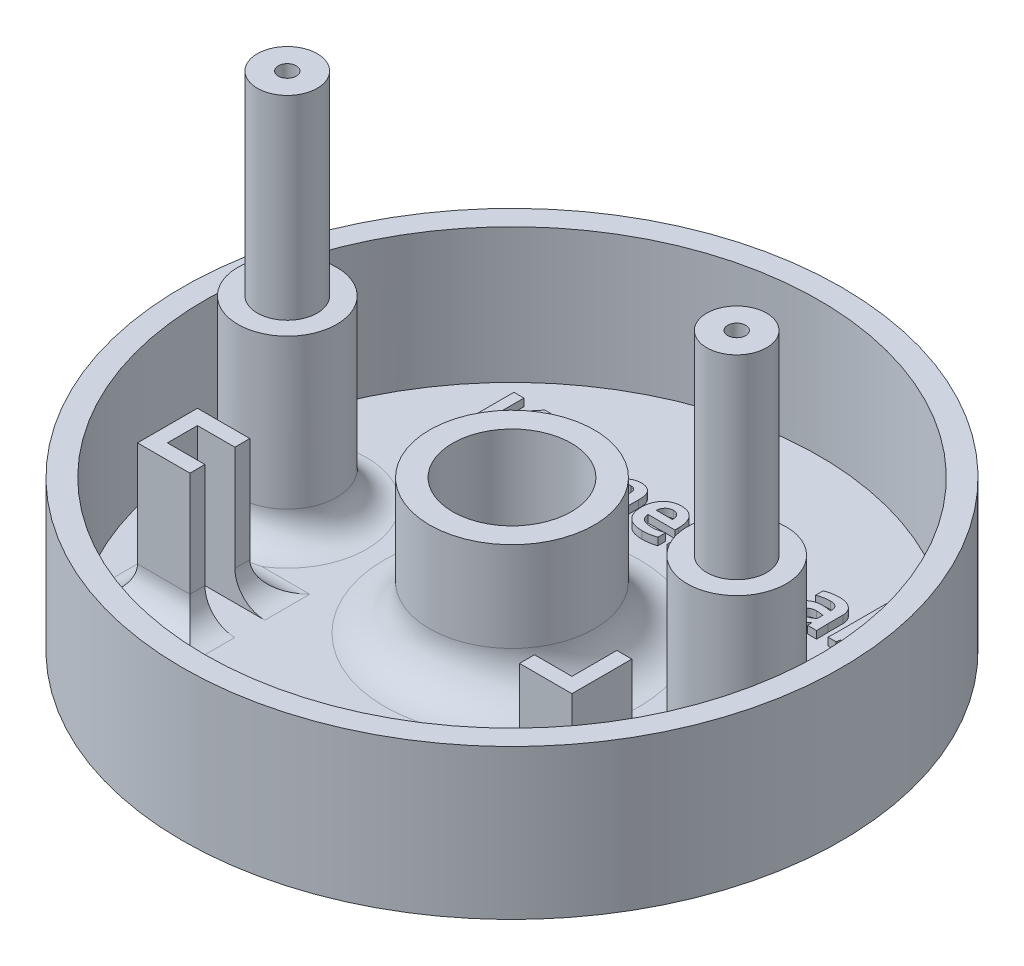
SolidWorks part; units mm, degrees
ref_plane "Front Plane" through (0, 0, 0) normal (0, 0, 1) x (1, 0, 0)
ref_plane "Top Plane" through (0, 0, 0) normal (0, 1, 0) x (1, 0, 0)
ref_plane "Right Plane" through (0, 0, 0) normal (1, 0, 0) x (0, 0, -1)
sketch "Sketch1" plane through (0, 0, 0) normal (0, 1, 0) x (1, 0, 0)
  line L0 (0, 0) -> (0, 22) construction
  line L1 (14.5, -6.5) -> (-14.5, -6.5)
  line L2 (-14.5, -6.5) -> (-14.5, -10.5)
  line L3 (-14.5, -10.5) -> (14.5, -10.5)
  line L4 (14.5, -10.5) -> (14.5, -6.5)
  line L5 (-11, -6.5) -> (-11, -7.5)
  line L6 (11, -6.5) -> (11, -7.5)
  line L9 (-11, -9.5) -> (-11, -10.5)
  line L10 (11, -9.5) -> (11, -10.5)
  line L13 (-13.5, -7.5) -> (13.5, -7.5)
  line L14 (-13.5, -7.5) -> (-13.5, -9.5)
  line L15 (-13.5, -9.5) -> (13.5, -9.5)
  line L16 (13.5, -7.5) -> (13.5, -9.5)
  line L17 (-13.5, -7.5) -> (13.5, -9.5) construction
  line L18 (-13.5, -9.5) -> (13.5, -7.5) construction
  circle A0 centre (-15, 0) radius 2
  circle A1 centre (0, 0) radius 20.5
  circle A2 centre (0, 0) radius 3.9639
  circle A3 centre (-15, 0) radius 0.6
  circle A4 centre (-15, 0) radius 3.3
  circle A10 centre (0, 0) radius 22
  circle A14 centre (0, 0) radius 5.5
  point P8 (0, 0)
  point P44 (0, 0)
  point P46 (0, -8.5)
  dimension "D1" = 1
  dimension "D2" = 1
  dimension "D8" = 3.5
  dimension "D10" = 4
  dimension "D3" = 15
  dimension "D11" = 1.2
  dimension "D4" = 27
  dimension "D5" = 2
  dimension "D6" = 1
  dimension "D7" = 1
  dimension "D9" = 3.5
extrude "Boss-Extrude1" add sketch "Sketch1" along normal blind 1 contours A10
extrude "Boss-Extrude2" add sketch "Sketch1<11>" along normal blind 10 contours A10 A1 | A14 A2 | L15 L14 L13 L5 L1 L2 L3 L9 | L13 L16 L15 L10 L3 L4 L1 L6 region at (14.4468, 0, 8.5) region at (-11.0532, 0, 7) region at (-21.3777, 0, 0) region at (-5.3444, 0, 0)
sketch "Sketch1<11>" plane through (0, 0, 0) normal (0, 1, 0) x (1, 0, 0) same geometry as "Sketch1"
fillet "Fillet1" radius 3 1 edges at (0, 1, 5.5)
fillet "Fillet6" radius 2 4 edges at (-12.75, 1, 6.5) (-14.5, 1, 8.5) (14.5, 1, 8.5) (12.75, 1, 6.5)
fillet "Fillet7" radius 2 6 edges at (11, 1, 6) (-11, 1, 6) (-13.75, 1, 10.5) (13.75, 1, 10.5) (-11, 1, 10) (11, 1, 10)
extrude "Cut-Extrude2" cut sketch "Sketch1<13>" along normal blind 10 contours A2
sketch "Sketch1<13>" plane through (0, 0, 0) normal (0, 1, 0) x (1, 0, 0) same geometry as "Sketch1"
fillet "Fillet10" radius 2 1 edges at (0, 0, 3.9639)
extrude "Boss-Extrude3" add sketch "Sketch1<14>" along normal blind 26 contours A0 A3 region at (-16.9434, 0, 0)
sketch "Sketch1<14>" plane through (0, 0, 0) normal (0, 1, 0) x (1, 0, 0) same geometry as "Sketch1"
extrude "Boss-Extrude4" add sketch "Sketch1<15>" along normal blind 13 contours A4 A0 region at (-18.2067, 0, 0)
sketch "Sketch1<15>" plane through (0, 0, 0) normal (0, 1, 0) x (1, 0, 0) same geometry as "Sketch1"
fillet "Fillet11" radius 2 1 edges at (-15, 1, 3.3)
mirror "Mirror1" about plane through (0, 0, 0) normal (1, 0, 0) of "Fillet11", "Boss-Extrude3", "Boss-Extrude4"
sketch "Sketch2" plane through (0, 0, 6.5) normal (0, 0, -1) x (-1, 0, 0)
  line L0 (-14.5, 10) -> (-11, 10) construction
  line L1 (-11, 3) -> (-13.5, 3)
  line L2 (-11, 3) -> (-11, 10)
  line L3 (-11, 10) -> (-13.5, 10)
  line L4 (-13.5, 3) -> (-13.5, 10)
extrude "Cut-Extrude3" cut sketch "Sketch2" against normal blind 1
sketch "Sketch3" plane through (0, 1, 0) normal (0, 1, 0) x (1, 0, 0)
  text T0 "KemereLab" font "Corbel" height in points 14
extrude "Boss-Extrude5" add sketch "Sketch3" along normal blind 0.5
